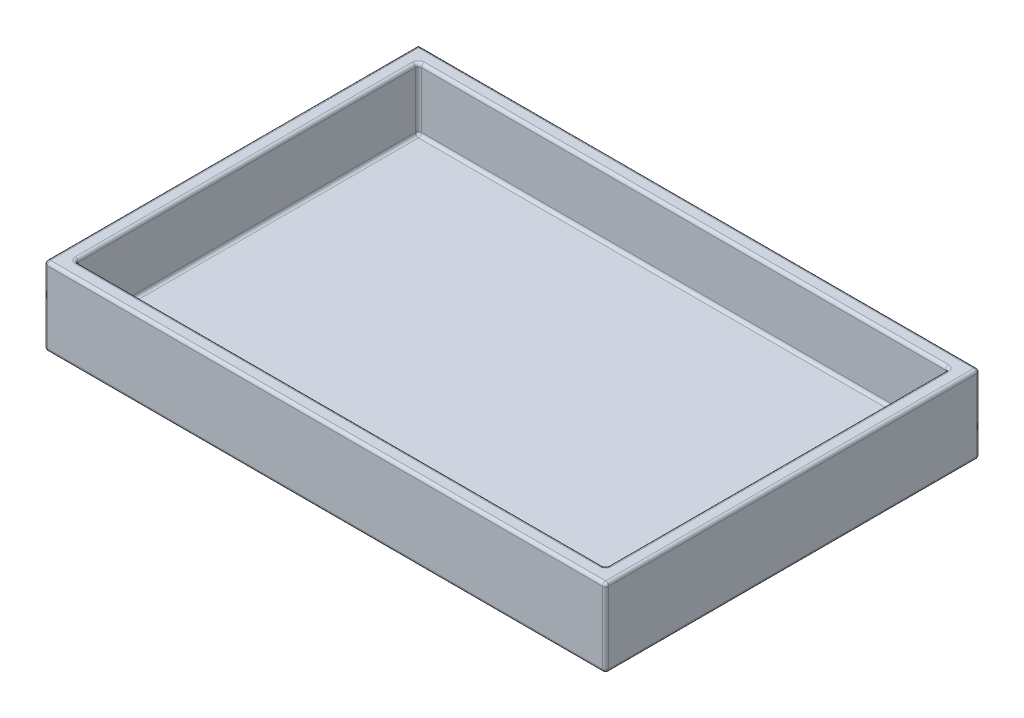
SolidWorks part; units mm, degrees
ref_plane "Front Plane" through (0, 0, 0) normal (0, 0, 1) x (1, 0, 0)
ref_plane "Top Plane" through (0, 0, 0) normal (0, 1, 0) x (1, 0, 0)
ref_plane "Right Plane" through (0, 0, 0) normal (1, 0, 0) x (0, 0, -1)
sketch "Sketch1" plane through (0, 0, 0) normal (0, 1, 0) x (1, 0, 0)
  line L1 (-113.0882, 37.0588) -> (66.9118, 37.0588)
  line L2 (-113.0882, 37.0588) -> (-113.0882, -82.9412)
  line L3 (-113.0882, -82.9412) -> (66.9118, -82.9412)
  line L4 (66.9118, 37.0588) -> (66.9118, -82.9412)
  dimension "D1" = 180
  dimension "D2" = 120
extrude "Boss-Extrude2" add sketch "Sketch1" along normal blind 25 contours L1 L4 L3 L2
sketch "Sketch3" plane through (0, 25, 0) normal (0, 1, 0) x (1, 0, 0)
  line L0 (66.9118, 37.0588) -> (66.9118, -82.9412) construction
  line L1 (-108.0882, 32.0588) -> (61.9118, 32.0588)
  line L2 (-108.0882, 32.0588) -> (-108.0882, -77.9412)
  line L3 (-108.0882, -77.9412) -> (61.9118, -77.9412)
  line L4 (61.9118, 32.0588) -> (61.9118, -77.9412)
  line L5 (-113.0882, 37.0588) -> (66.9118, 37.0588) construction
  dimension "D1" = 170
  dimension "D2" = 110
  dimension "D3" = 5
  dimension "D4" = 5
extrude "Cut-Extrude2" cut sketch "Sketch3" against normal blind 20 contours L3 L4 L1 L2
fillet "Fillet6" radius 1 23 edges at (-23.0882, 0, -37.0588) (-113.0882, 0, 22.9412) (61.9118, 15, 77.9412) (61.9118, 5, 22.9412) (61.9118, 15, -32.0588) (-108.0882, 15, 77.9412) (-23.0882, 5, 77.9412) (-23.0882, 0, 82.9412) (-113.0882, 12.5, 82.9412) (66.9118, 12.5, -37.0588) (66.9118, 12.5, 82.9412) (66.9118, 0, 22.9412) (66.9118, 25, 22.9412) (61.9118, 25, 22.9412) (-23.0882, 5, -32.0588) (-108.0882, 5, 22.9412) (-108.0882, 15, -32.0588) (-23.0882, 25, -32.0588) (-108.0882, 25, 22.9412) (-23.0882, 25, 77.9412) (-23.0882, 25, 82.9412) (-113.0882, 25, 22.9412) (-23.0882, 25, -37.0588)
equation "\"boxlengthout\"= 180"
equation "\"boxwidthout\" = 120"
equation "\"D1@Sketch1\"= \"boxlengthout\""
equation "\"D2@Sketch1\"= \"boxwidthout\""
equation "\"D1@Sketch3\"=\"boxlengthout\"-10"
equation "\"D2@Sketch3\"=\"boxwidthout\"-10"
equation "\"D3@Sketch3\"=(\"boxlengthout\"-\"D1@Sketch3\")/2"
equation "\"D4@Sketch3\"=(\"boxwidthout\"-\"D2@Sketch3\")/2"
